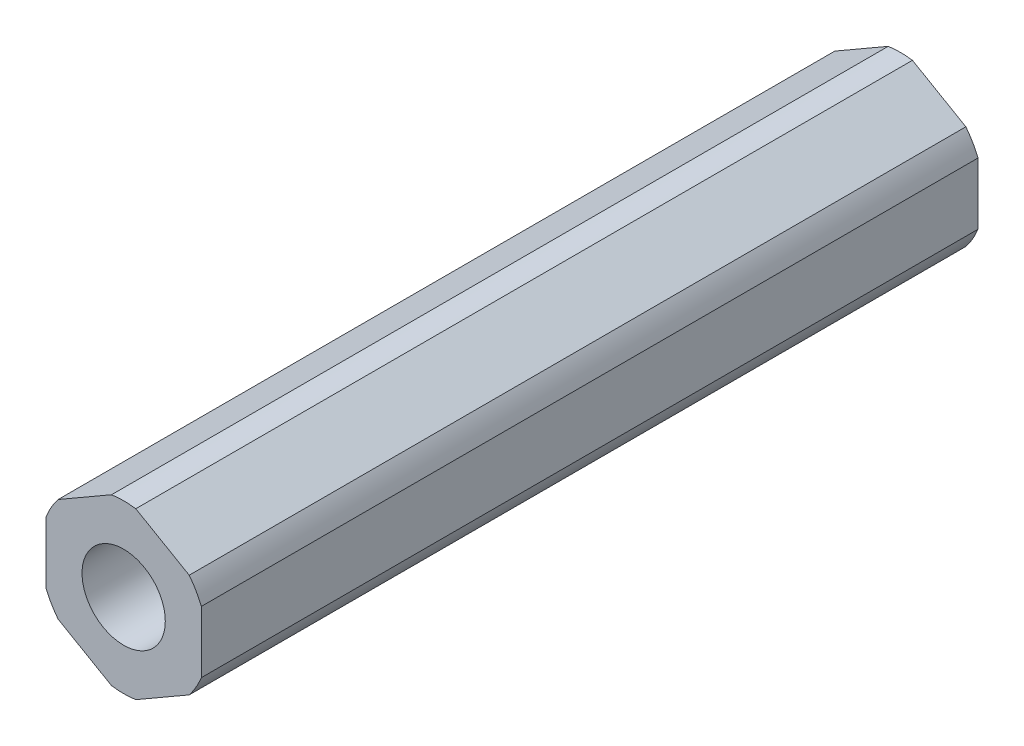
SolidWorks part; units mm, degrees
material "ThunderHex"
ref_plane "Front Plane" through (0, 0, 0) normal (0, 0, 1) x (1, 0, 0)
ref_plane "Top Plane" through (0, 0, 0) normal (0, 1, 0) x (1, 0, 0)
ref_plane "Right Plane" through (0, 0, 0) normal (1, 0, 0) x (0, 0, -1)
ref_plane "End1" through (0, 0, 23.8125) normal (0, 0, 1) x (1, 0, 0)
ref_plane "End2" through (0, 0, -23.8125) normal (0, 0, 1) x (1, 0, 0)
sketch "Sketch1" plane through (0, 0, 0) normal (0, 0, 1) x (1, 0, 0)
  circle A0 centre (0, 0) radius 4.7625
  dimension "D1" = 9.525
extrude "Basic Rod" add sketch "Sketch1" along normal up to surface (23.8125 mm away) and the other way up to surface (23.8125 mm away) up to plane "End1" other way up to plane "End2"
ref_axis "Center Axis" through (0, 0, -38.2778) along (0, 0, 1)
sketch "Sketch8" plane through (0, 0, 0) normal (0, 0, 1) x (1, 0, 0)
  line L0 (-4.0195, 3.1786) -> (-4.7625, 2.7496) construction
  line L1 (-0.743, 5.0703) -> (-4.0195, 3.1786)
  line L2 (-4.7625, 1.8917) -> (-4.7625, -1.8917)
  line L3 (-4.0195, -3.1786) -> (-0.743, -5.0703)
  line L4 (0.743, -5.0703) -> (4.0195, -3.1786)
  line L5 (4.7625, -1.8917) -> (4.7625, 1.8917)
  line L6 (4.0195, 3.1786) -> (0.743, 5.0703)
  line L7 (-4.7625, 2.7496) -> (-4.7625, 1.8917) construction
  line L8 (0, 5.4993) -> (-0.743, 5.0703) construction
  line L9 (0.743, 5.0703) -> (0, 5.4993) construction
  line L10 (4.7625, 2.7496) -> (4.0195, 3.1786) construction
  line L11 (4.7625, 1.8917) -> (4.7625, 2.7496) construction
  line L12 (4.7625, -2.7496) -> (4.7625, -1.8917) construction
  line L13 (4.0195, -3.1786) -> (4.7625, -2.7496) construction
  line L14 (0, -5.4993) -> (0.743, -5.0703) construction
  line L15 (-0.743, -5.0703) -> (0, -5.4993) construction
  line L16 (-4.7625, -2.7496) -> (-4.0195, -3.1786) construction
  line L17 (-4.7625, -1.8917) -> (-4.7625, -2.7496) construction
  circle A0 centre (0, 0) radius 4.7625 construction
  arc A1 (-4.7625, -1.8917) -> (-4.0195, -3.1786) centre (0, 0) ccw
  circle A2 centre (0, 0) radius 4.7625 construction
  arc A3 (-4.7625, 1.8917) -> (-4.7625, -1.8917) centre (0, 0) ccw construction
  arc A4 (-0.743, 5.0703) -> (-4.0195, 3.1786) centre (0, 0) ccw construction
  arc A5 (-4.0195, 3.1786) -> (-4.7625, 1.8917) centre (0, 0) ccw
  arc A6 (4.0195, 3.1786) -> (0.743, 5.0703) centre (0, 0) ccw construction
  arc A7 (0.743, 5.0703) -> (-0.743, 5.0703) centre (0, 0) ccw
  arc A8 (4.7625, -1.8917) -> (4.7625, 1.8917) centre (0, 0) ccw construction
  arc A9 (4.7625, 1.8917) -> (4.0195, 3.1786) centre (0, 0) ccw
  arc A10 (0.743, -5.0703) -> (4.0195, -3.1786) centre (0, 0) ccw construction
  arc A11 (4.0195, -3.1786) -> (4.7625, -1.8917) centre (0, 0) ccw
  arc A12 (-4.0195, -3.1786) -> (-0.743, -5.0703) centre (0, 0) ccw construction
  arc A13 (-0.743, -5.0703) -> (0.743, -5.0703) centre (0, 0) ccw
  dimension "D1" = 10.2489
extrude "THex" add sketch "Sketch8" along normal mid plane 47.625
sketch "Sketch5" plane through (0, 0, 0) normal (0, 0, 1) x (1, 0, 0)
  line L1 (-2.7496, 4.7625) -> (-5.4993, 0)
  line L2 (-5.4993, 0) -> (-2.7496, -4.7625)
  line L3 (-2.7496, -4.7625) -> (2.7496, -4.7625)
  line L4 (2.7496, -4.7625) -> (5.4993, 0)
  line L5 (5.4993, 0) -> (2.7496, 4.7625)
  line L6 (2.7496, 4.7625) -> (-2.7496, 4.7625)
  circle A0 centre (0, 0) radius 4.7625 construction
  circle A2 centre (0, 0) radius 4.7625 construction
extrude "Hex" [suppressed] add sketch "Sketch5" along normal mid plane 47.625
sketch "Sketch7" plane through (0, 0, 0) normal (1, 0, 0) x (0, 0, -1)
  line L0 (0, 0) -> (-50000, 0) construction
  line L1 (-23.8125, 4.4704) -> (-24.8285, 4.4704)
  line L2 (-24.8285, 4.4704) -> (-24.8285, 4.7625)
  line L3 (-24.8285, 4.7625) -> (-25.8445, 4.7625)
  line L4 (-26.3525, 4.2545) -> (-26.3525, 0)
  line L5 (-26.3525, 0) -> (-23.8125, 0)
  line L6 (-23.8125, 0) -> (-23.8125, 4.4704)
  line L7 (-25.8445, 4.7625) -> (-26.3525, 4.2545)
  line L8 (38.2778, 0) -> (-38.2778, 0) construction
  line L9 (-23.8125, 5.2388) -> (-23.8125, -5.2388) construction
  point P7 (-26.3525, 4.7625)
  dimension "D1" = 9.525
  dimension "D4" = 1.016
  dimension "D2" = 0.2921
  dimension "D3" = 2.54
revolve "1stSnapRing" [suppressed] add sketch "Sketch7" angle 360 about axis through (0, 0, -38.2778) along (0, 0, 1)
mirror "2ndSnapRing" [suppressed] about plane through (0, 0, 0) normal (0, 0, 1)
sketch "Sketch2" plane through (0, 0, 0) normal (0, 0, 1) x (1, 0, 0)
  circle A0 centre (0, 0) radius 2.5527
  dimension "D1" = 5.1054
extrude "Internal Cut" cut sketch "Sketch2" against normal through all both and the other way through all
equation "\"Unit Measure\"= \"Length\"'in"
equation "\"D1@Sketch1\"=\"OD\""
equation "\"D1\"= \"Length\""
equation "\"D1@Sketch2\"=\"ID\""
equation "\"Internal Cut\"= IIF ( \"ID\" = 0 ,  suppressed  ,  unsuppressed  ) "
equation "\"D1@Hex\" = \"Length\""
equation "\"Hex\" = IIF ( \"SelectionType\" = 1 , \"suppressed\" , iif ( \"SelectionType\" = 2 , \"suppressed\" , \"unsuppressed\" ) )"
equation "\"OutsideDiameter\"= \"OD\"'in"
equation "\"ThunderHexDia\"= iif ( \"OD\" < .36 , \"OD\" * 1.1 , iif ( \"OD\" < .40 , .4035 , iif ( \"OD\" < .52 , .5415 , \"OD\" * 1.1 ) ) )"
equation "\"D1@Sketch7\"=\"Thickness\""
equation "\"SRDia\"= iif ( \"OD\" = .5 , ( \"OD\" - .468 ) / 2 , iif ( \"OD\" = .375 , ( \"OD\" - .352 ) / 2 , .050 ) )"
equation "\"D2@Sketch7\"= \"SnapRingDepth\""
equation "\"1stSnapRing\"= iif ( \"SnapRingCount\" > 0 , \"unsuppressed\" , \"suppressed\" )"
equation "\"2ndSnapRing\"= iif ( \"SnapRingCount\" = 2 , \"unsuppressed\" , \"suppressed\" )"
equation "\"D1@End1\" = \"Length\" / 2"
equation "\"D1@End2\" = \"Length\""
equation "\"D1@Sketch8\"=\"ThunderHexDia\""
equation "\"D1@THex\" = \"Length\""
equation "\"THex\"= IIF ( \"SelectionType\" = 0 ,  suppressed  , iif ( \"SelectionType\" = 2 ,  suppressed  ,  unsuppressed  )  ) "
